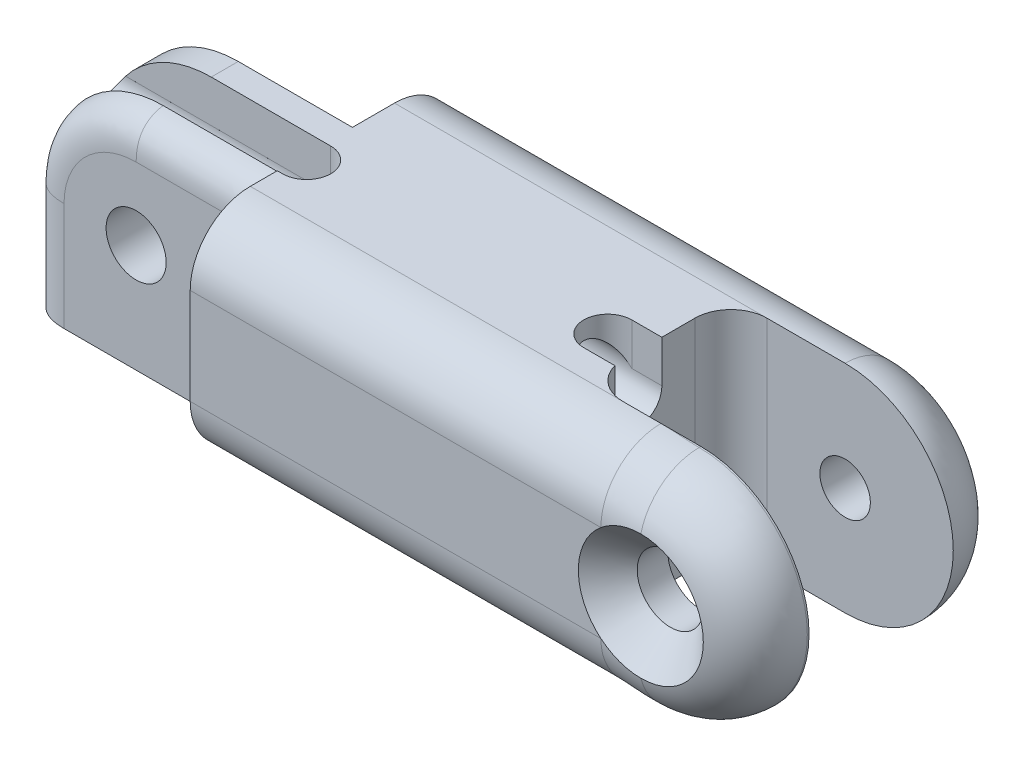
SolidWorks part; units mm, degrees
ref_plane "Front Plane" through (0, 0, 0) normal (0, 0, 1) x (1, 0, 0)
ref_plane "Top Plane" through (0, 0, 0) normal (0, 1, 0) x (1, 0, 0)
ref_plane "Right Plane" through (0, 0, 0) normal (1, 0, 0) x (0, 0, -1)
sketch "Sketch2" plane through (0, 0, 0) normal (0, 1, 0) x (1, 0, 0)
  line L0 (-14, 11) -> (32.5, 11)
  line L1 (32.5, 11) -> (32.5, 6)
  line L2 (32.5, 6) -> (17, 6)
  line L3 (14, 3) -> (14, -3)
  line L4 (17, -6) -> (32.5, -6)
  line L5 (32.5, -6) -> (32.5, -11)
  line L7 (-32.5, -6) -> (-32.5, 2.5)
  line L8 (-49.3622, 0) -> (56.3776, 0) construction
  line L9 (0, 21.2372) -> (0, -19.0689) construction
  line L10 (14, 3) -> (17, 3) construction
  line L11 (17, 3) -> (17, 6) construction
  line L16 (-14, -11) -> (32.5, -11)
  line L18 (-32.5, -6) -> (-14, -6)
  line L19 (-14, -6) -> (-14, -11)
  line L20 (-32.5, 2.5) -> (-14, 2.5)
  line L21 (-14, 2.5) -> (-14, 11)
  arc A0 (17, 6) -> (14, 3) centre (17, 3) ccw
  arc A1 (17, -6) -> (14, -3) centre (17, -3) cw
  point P13 (17, 3)
  dimension "D1" = 65
  dimension "D2" = 22
  dimension "D3" = 5
  dimension "D4" = 18.5
  dimension "D5" = 12
  dimension "D6" = 3
  dimension "D7" = 3
  dimension "D8" = 8.5
  dimension "D9" = 5
  dimension "D10" = 8.5
  dimension "D11" = 18.5
extrude "Boss-Extrude1" add sketch "Sketch2" along normal blind 18
sketch "Sketch5" plane through (0, 0, 11) normal (0, 0, 1) x (1, 0, 0)
  line L0 (-32.5, 9) -> (31.8491, 9) construction
  line L1 (-23.5, 18) -> (-23.5, 0) construction
  line L2 (32.5, 18) -> (32.5, 0) construction
  line L3 (-14, 18) -> (32.5, 18) construction
  line L4 (23.5, 18) -> (23.5, 0) construction
  line L5 (-32.5, 18) -> (-32.5, 0) construction
  line L6 (-32.5, 9) -> (-32.5, 0)
  line L7 (-32.5, 18) -> (-14, 18) construction
  line L8 (-32.5, 0) -> (23.5, 0)
  line L9 (-23.5, 18) -> (23.5, 18)
  arc A0 (-23.5, 18) -> (-32.5, 9) centre (-23.5, 9) ccw
  arc A1 (23.5, 0) -> (23.5, 18) centre (23.5, 9) ccw
  circle A2 centre (-23.5, 9) radius 2.5
  dimension "D2" = 5
  dimension "D1" = 9
extrude "Cut-Extrude1" cut sketch "Sketch5" against normal blind 22 flip side to cut
sketch "Sketch6" plane through (0, 0, 11) normal (0, 0, 1) x (1, 0, 0)
  line L0 (23.5, 0) -> (23.5, 18) construction
  point P4 (23.5, 9)
hole_wizard "CSK for M5 Countersunk Flat Head Screw1" positions "Sketch7" profile "Sketch8" countersink size "M5" standard "DIN" end condition up to next
sketch "Sketch7" plane through (0, 0, 11) normal (0, 0, 1) x (1, 0, 0)
  point P0 (23.5, 9)
sketch "Sketch8" plane through (23.5, 9, 11) normal (1, 0, 0) x (0, -1, 0)
  line L0 (0, 0) -> (0, 5)
  line L1 (0, 5) -> (2.75, 5)
  line L2 (2.75, 5) -> (2.75, 2.45)
  line L3 (2.75, 2.45) -> (5.2, 0)
  line L5 (5.2, 0) -> (0, 0)
  line L6 (-2.75, 2.45) -> (-5.2, 0) construction
  line L11 (0, -6.35) -> (0, 107.95) construction
  dimension "Thru Hole Dia." = 5.5
  dimension "Thru Hole Depth" = 5
  dimension "Near C'Sink Dia." = 10.4
  dimension "Near C'Sink Angle" = 90
hole_wizard "M5 Tapped Hole1" positions "Sketch9" profile "Sketch11" tap size "M5" standard "DIN" end condition through all
sketch "Sketch9" plane through (0, 0, 11) normal (0, 0, 1) x (1, 0, 0)
  point P0 (23.5, 9)
sketch "Sketch11" plane through (23.5, 9, 11) normal (1, 0, 0) x (0, -1, 0)
  line L0 (0, 0) -> (0, 22)
  line L1 (0, 22) -> (2.1, 22)
  line L2 (2.1, 22) -> (2.1, 3.1)
  line L3 (2.1, 3.1) -> (5.2, 0)
  line L5 (5.2, 0) -> (0, 0)
  line L6 (-2.1, 3.1) -> (-5.2, 0) construction
  line L11 (0, -6.35) -> (0, 107.95) construction
  dimension "Thru Tap Drill Dia." = 4.2
  dimension "Thru Tap Drill Depth" = 22
  dimension "Near C'Sink Dia." = 10.4
  dimension "Near C'Sink Angle" = 90
cosmetic thread "Hole Thread1" parameters "D2"=5
fillet "Fillet3" radius 3 3 edges at (-32.5, 4.5, 6) (-18.75, 18, 6) (-29.864, 15.364, 6) conic rho 0.5
sketch "Sketch13" plane through (14, 0, 0) normal (1, 0, 0) x (0, 0, -1)
  line L0 (-1.75, 21.4915) -> (-1.75, -4.5302) construction
  line L1 (-3, 18) -> (3, 18) construction
  circle A0 centre (-1.75, 14.5) radius 2
  dimension "D2" = 4
  dimension "D3" = 3.5
  dimension "D1" = 1.75
extrude "Cut-Extrude2" cut sketch "Sketch13" against normal through all both and the other way through all
sketch "Sketch14" plane through (0, 18, 0) normal (0, 1, 0) x (1, 0, 0)
  line L0 (-30.6236, 0.2504) -> (-13.5557, 0.2504)
  line L1 (-30.5557, -3.75) -> (-13.5557, -3.75)
  line L3 (-30.5557, -3.75) -> (-30.6236, 0.2504)
  arc A0 (-13.5557, -3.75) -> (-13.5557, 0.2504) centre (-13.5557, -1.7498) ccw
  spline S1 degree 3 poles (-29.0797, -3) (-28.9473, -2.8693) (-28.8242, -2.7233) (-28.6669, -2.4679) (-28.62, -2.3776) (-28.5431, -2.1872) (-28.5127, -2.0851) (-28.4764, -1.8774) (-28.4703, -1.7698) (-28.4841, -1.5572) (-28.5036, -1.4537) (-28.5944, -1.1509) (-28.6934, -0.9724) (-28.9222, -0.6565) (-29.0506, -0.5207) (-29.3219, -0.2789) (-29.4619, -0.1762) (-29.8834, 0.0849) (-30.1717, 0.1991) (-30.5706, 0.2557) (-30.7006, 0.2556) (-30.9459, 0.209) (-31.0594, 0.1634) (-31.269, 0.0188) (-31.3624, -0.0793) (-31.5226, -0.3256) (-31.5911, -0.4779) (-31.6703, -0.7331) (-31.6932, -0.8231) (-31.7322, -1.0133) (-31.7481, -1.1133) (-31.7724, -1.3157) (-31.781, -1.419) (-31.7912, -1.6301) (-31.7926, -1.7379) (-31.7863, -2.055) (-31.7677, -2.2665) (-31.7021, -2.6575) (-31.6546, -2.8399) (-31.5922, -3) knots 0 0 0 0 0.0625 0.0625 0.09375 0.09375 0.125 0.125 0.15625 0.15625 0.1875 0.1875 0.25 0.25 0.3125 0.3125 0.375 0.375 0.5 0.5 0.5625 0.5625 0.625 0.625 0.6875 0.6875 0.75 0.75 0.78125 0.78125 0.8125 0.8125 0.84375 0.84375 0.875 0.875 0.9375 0.9375 1 1 1 1 construction
  spline S2 degree 3 poles (-31.5922, -3) (-31.5381, -3.1387) (-31.4701, -3.2552) (-31.3108, -3.4526) (-31.2195, -3.5323) (-31.0254, -3.6532) (-30.9205, -3.6957) (-30.705, -3.7461) (-30.594, -3.7546) (-30.2507, -3.7337) (-30.0173, -3.6588) (-29.5422, -3.4019) (-29.3092, -3.2263) (-29.0797, -3) knots 0 0 0 0 0.125 0.125 0.25 0.25 0.375 0.375 0.5 0.5 0.75 0.75 1 1 1 1 construction
  dimension "D2" = 2.0002
  dimension "D1" = 17
extrude "Cut-Extrude3" cut sketch "Sketch14" against normal blind 3.5
sketch "Sketch15" plane through (0, 18, 0) normal (0, 1, 0) x (1, 0, 0)
sketch "Sketch16" plane through (0, 18, 0) normal (0, 1, 0) x (1, 0, 0)
  line L0 (-8.0769, -1.75) -> (29.6251, -1.75) construction
  line L1 (11.5, 0.25) -> (19.0559, 0.25)
  line L3 (11.5, -3.75) -> (19.0559, -3.75)
  line L4 (19.0559, 0.25) -> (19.0559, -3.75)
  line L5 (14, -3) -> (14, 3) construction
  arc A0 (11.5, 0.25) -> (11.5, -3.75) centre (11.5, -1.75) ccw
  dimension "D2" = 4
  dimension "D1" = 1.75
  dimension "D3" = 2.5
extrude "Cut-Extrude4" cut sketch "Sketch16" against normal blind 3.5
fillet "Fillet4" radius 5 5 edges at (4.75, 0, -11) (32.5, 9, -11) (4.75, 0, 11) (4.75, 18, -11) (4.75, 18, 11)
